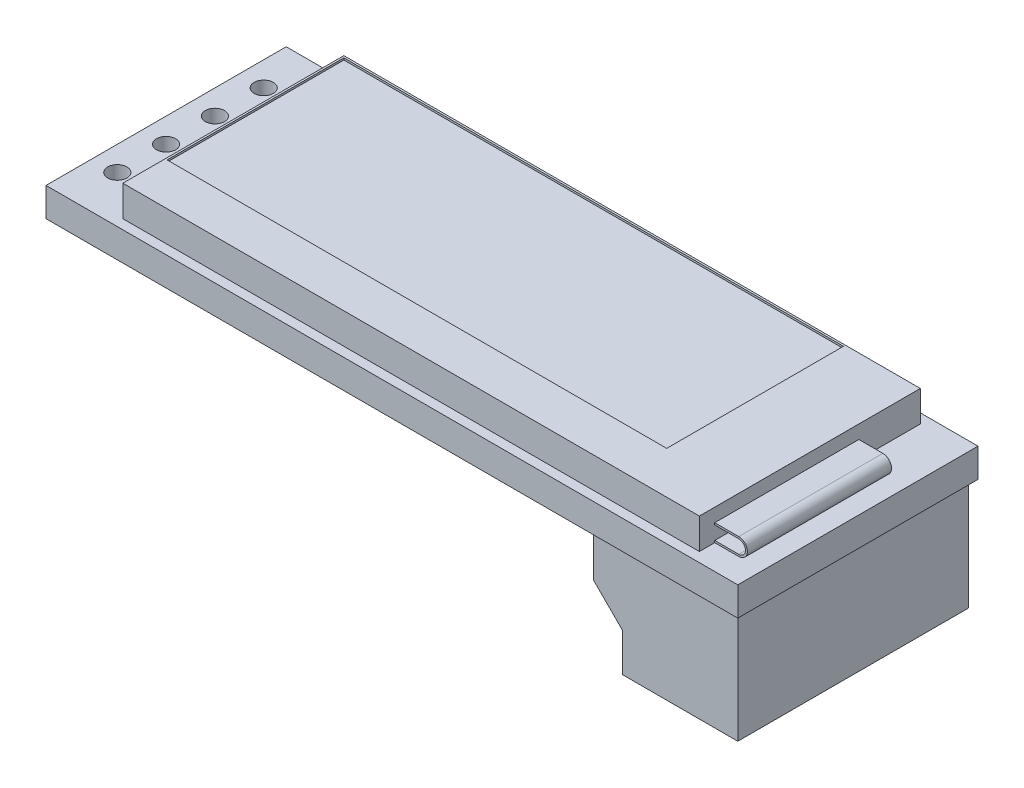
SolidWorks part; units mm, degrees
ref_plane "Front Plane" through (0, 0, 0) normal (0, 0, 1) x (1, 0, 0)
ref_plane "Top Plane" through (0, 0, 0) normal (0, 1, 0) x (1, 0, 0)
ref_plane "Right Plane" through (0, 0, 0) normal (1, 0, 0) x (0, 0, -1)
sketch "Sketch1" plane through (0, 0, 0) normal (0, 1, 0) x (1, 0, 0)
  line L1 (18, 6.25) -> (-18, 6.25)
  line L2 (18, 6.25) -> (18, -6.25)
  line L3 (18, -6.25) -> (-18, -6.25)
  line L4 (-18, 6.25) -> (-18, -6.25)
  line L5 (18, 6.25) -> (-18, -6.25) construction
  line L6 (18, -6.25) -> (-18, 6.25) construction
  point P0 (0, 0)
  dimension "D1" = 36
  dimension "D2" = 12.5
extrude "Boss-Extrude1" add sketch "Sketch1" along normal blind 1.5
sketch "Sketch2" plane through (0, 1.5, 0) normal (0, 1, 0) x (1, 0, 0)
  line L0 (-18, 6.25) -> (-18, -6.25) construction
  line L1 (-18, -6.25) -> (18, -6.25) construction
  circle A0 centre (-16.73, -3.81) radius 0.5
  dimension "D2" = 2.44
  dimension "D3" = 1
  dimension "D1" = 1.27
extrude "Cut-Extrude1" cut sketch "Sketch2" against normal through all
pattern_linear "LPattern1" count 4 spacing 2.54 along (0, 0, -1) of "Cut-Extrude1"
sketch "Sketch3" plane through (0, 0, 0) normal (0, -1, 0) x (1, 0, 0)
  line L0 (18, 6.25) -> (18, -6.25) construction
  line L1 (17.75, -6) -> (10.25, -6)
  line L2 (17.75, -6) -> (17.75, 6)
  line L3 (17.75, 6) -> (10.25, 6)
  line L4 (10.25, -6) -> (10.25, 6)
  line L5 (17.75, -6) -> (10.25, 6) construction
  line L6 (17.75, 6) -> (10.25, -6) construction
  line L7 (18, -6.25) -> (-18, -6.25) construction
  point P0 (14, 0)
  dimension "D1" = 0.25
  dimension "D2" = 7.5
  dimension "D3" = 0.25
extrude "Boss-Extrude2" add sketch "Sketch3" along normal blind 5.8
sketch "Sketch4" plane through (0, 0, 6) normal (0, 0, 1) x (1, 0, 0)
  line L1 (10.25, -5.8) -> (11.75, -5.8)
  line L2 (10.25, -5.8) -> (10.25, -3.8)
  line L3 (10.25, -3.8) -> (11.75, -3.8)
  line L4 (11.75, -5.8) -> (11.75, -3.8)
  dimension "D1" = 1.5
  dimension "D2" = 2
extrude "Cut-Extrude2" cut sketch "Sketch4" against normal through all
chamfer "Chamfer1" distance 1.5 angle 45 1 edges at (10.25, -3.8, 0)
sketch "Sketch5" plane through (0, 1.5, 0) normal (0, 1, 0) x (1, 0, 0)
  line L0 (-18, 6.25) -> (-18, -6.25) construction
  line L1 (15.5, 5.75) -> (-14.5, 5.75)
  line L2 (15.5, 5.75) -> (15.5, -5.75)
  line L3 (15.5, -5.75) -> (-14.5, -5.75)
  line L4 (-14.5, 5.75) -> (-14.5, -5.75)
  line L5 (15.5, 5.75) -> (-14.5, -5.75) construction
  line L6 (15.5, -5.75) -> (-14.5, 5.75) construction
  point P0 (0.5, 0)
  dimension "D1" = 30
  dimension "D2" = 11.5
  dimension "D3" = 3.5
extrude "Boss-Extrude3" add sketch "Sketch5" along normal blind 1.6
sketch "Sketch6" plane through (0, 0, 5.75) normal (0, 0, 1) x (1, 0, 0)
  line L0 (15.5, 1.5) -> (16.75, 1.5)
  line L1 (-18, 1.5) -> (18, 1.5) construction
  line L2 (16.75, 2.4) -> (15.5, 2.4)
  line L3 (15.5, 3.1) -> (15.5, 1.5) construction
  line L4 (18, 1.5) -> (18, 0) construction
  line L5 (-14.5, 3.1) -> (15.5, 3.1) construction
  arc A0 (16.75, 1.5) -> (16.75, 2.4) centre (16.75, 1.95) ccw
  dimension "D1" = 0.8
  dimension "D2" = 0.7
extrude "Extrude-Thin1" add sketch "Sketch6" against normal blind 7.5 from offset 0.8 thin offset against normal yes thin type one direction reverse wall 0.1
sketch "Sketch7" plane through (0, 3.1, 0) normal (0, 1, 0) x (1, 0, 0)
  line L0 (-14.5, -5.75) -> (15.5, -5.75) construction
  line L1 (11.6, -3.55) -> (-14.4, -3.55)
  line L2 (11.6, -3.55) -> (11.6, 5.65)
  line L3 (11.6, 5.65) -> (-14.4, 5.65)
  line L4 (-14.4, -3.55) -> (-14.4, 5.65)
  line L5 (11.6, -3.55) -> (-14.4, 5.65) construction
  line L6 (11.6, 5.65) -> (-14.4, -3.55) construction
  line L7 (-14.5, 5.75) -> (-14.5, -5.75) construction
  line L8 (15.5, 5.75) -> (-14.5, 5.75) construction
  point P0 (-1.4, 1.05)
  dimension "D1" = 2.2
  dimension "D2" = 0.1
  dimension "D3" = 0.1
  dimension "D4" = 26
extrude "Cut-Extrude3" cut sketch "Sketch7" against normal blind 0.1
equation "\"D3@Sketch3\"=\"D1@Sketch3\""
equation "\"D3@Sketch7\"=\"D2@Sketch7\""
